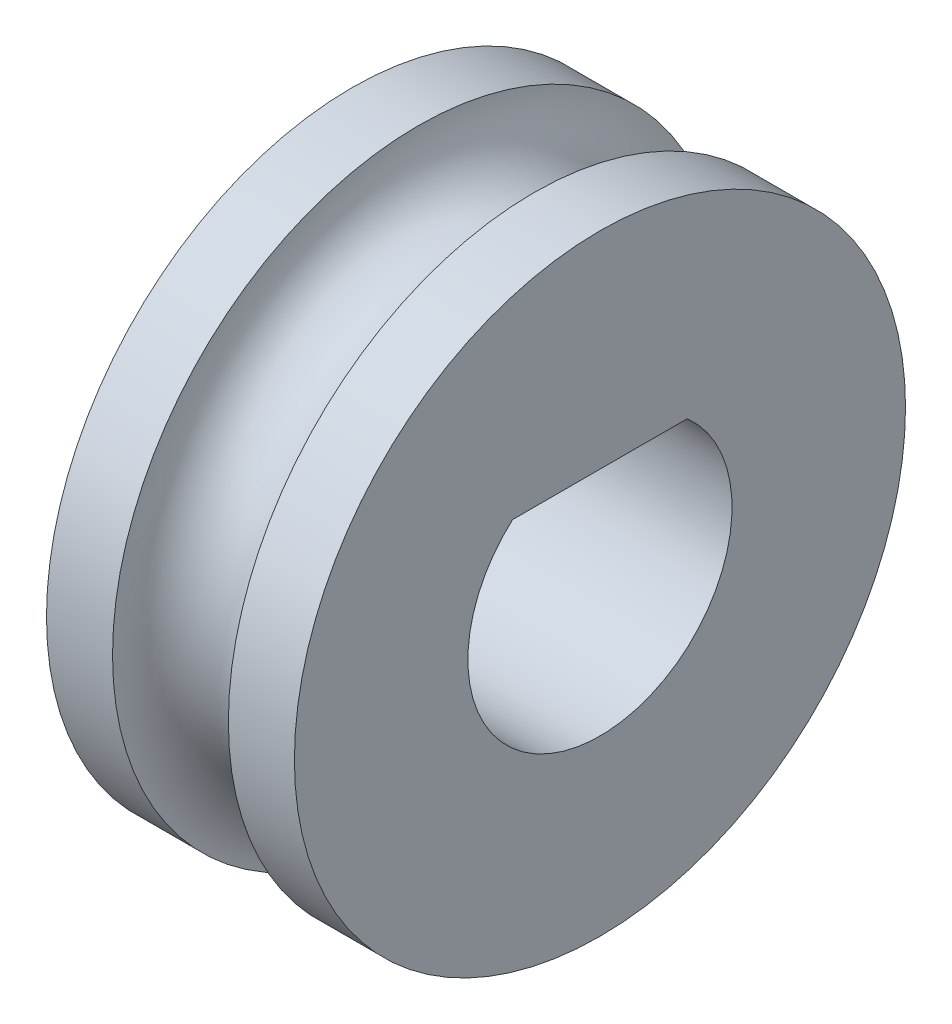
SolidWorks part; units mm, degrees
ref_plane "Front Plane" through (0, 0, 0) normal (0, 0, 1) x (1, 0, 0)
ref_plane "Top Plane" through (0, 0, 0) normal (0, 1, 0) x (1, 0, 0)
ref_plane "Right Plane" through (0, 0, 0) normal (1, 0, 0) x (0, 0, -1)
sketch "Sketch3" plane through (0, 0, 0) normal (0, 0, 1) x (1, 0, 0)
  line L0 (0, 0) -> (0, 9.254) construction
  line L1 (1.754, 0) -> (-1.754, 0)
  line L2 (-1.754, 0) -> (-1.754, 9.254)
  line L3 (1.754, 0) -> (1.754, 9.254)
  arc A0 (-1.754, 9.254) -> (1.754, 9.254) centre (0, 9.254) ccw
  dimension "D1" = 9.254
  dimension "D2" = 1.754
revolve "Revolve1" add sketch "Sketch3" angle 360 about L1
sketch "Sketch4" plane through (-1.754, 0, 0) normal (-1, 0, 0) x (0, 0, 1)
  line L0 (0, 0) -> (0, 4) construction
  line L1 (0, 3.254) -> (2.7401, 3.254)
  line L2 (0, 3) -> (-2.6458, 3)
  line L3 (0, 3) -> (2.6458, 3)
  line L4 (0, 3.254) -> (-2.7401, 3.254)
  arc A0 (-2.6458, 3) -> (2.6458, 3) centre (0, 0) ccw
  arc A1 (-2.7401, 3.254) -> (2.7401, 3.254) centre (0, 0) ccw
  dimension "D1" = 8
  dimension "D2" = 1
  dimension "D3" = 0.254
extrude "Cut-Extrude1" cut sketch "Sketch4" against normal through all contours L2 A0 L3
ref_axis "Axis1" through (1.754, 0, 0) along (-1, 0, 0)
sketch "Sketch5" plane through (-1.754, 0, 0) normal (-1, 0, 0) x (0, 0, 1)
  line L0 (2.6458, 3) -> (-2.6458, 3) construction
  line L1 (2.6458, 3) -> (-2.6458, 3)
  arc A0 (-2.6458, 3) -> (2.6458, 3) centre (0, 0) ccw construction
  circle A1 centre (0, 0) radius 9.254
  circle A2 centre (0, 0) radius 9.254
  arc A3 (-2.6458, 3) -> (2.6458, 3) centre (0, 0) ccw
  dimension "D1" = 0
extrude "Boss-Extrude1" add sketch "Sketch5" along normal blind 2
mirror "Mirror1" about plane through (0, 0, 0) normal (1, 0, 0) of "Boss-Extrude1"
